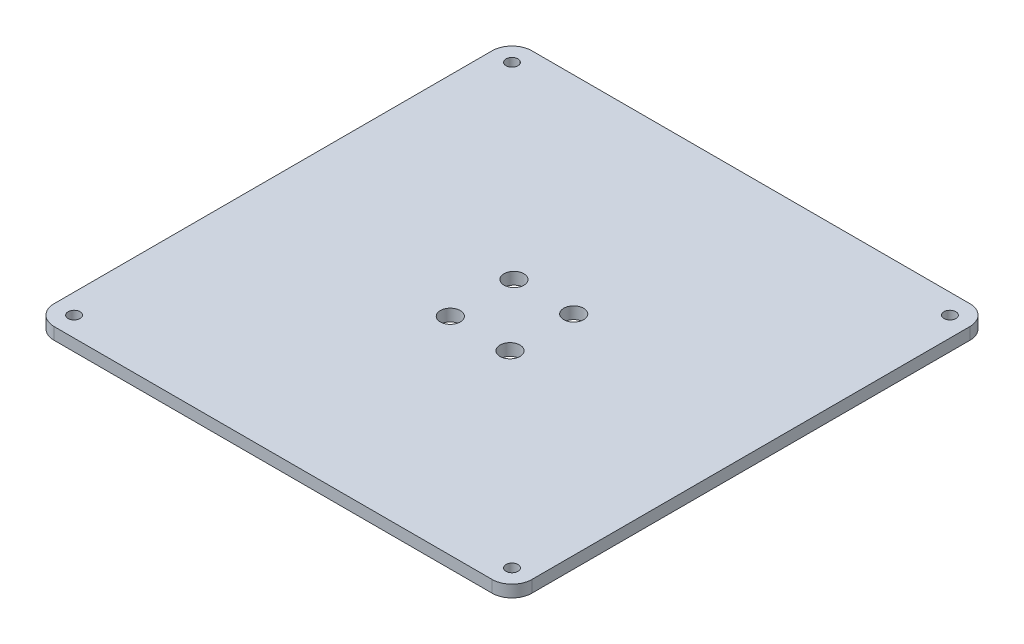
SolidWorks part; units mm, degrees
ref_plane "Alzado" through (0, 0, 0) normal (0, 0, 1) x (1, 0, 0)
ref_plane "Planta" through (0, 0, 0) normal (0, 1, 0) x (1, 0, 0)
ref_plane "Vista lateral" through (0, 0, 0) normal (1, 0, 0) x (0, 0, -1)
sketch "Sketch1" plane through (0, 0, 0) normal (0, 1, 0) x (1, 0, 0)
  line L1 (-7.5, -8) -> (7.5, -8) construction
  line L2 (-7.5, -8) -> (-7.5, 8) construction
  line L3 (-7.5, 8) -> (7.5, 8) construction
  line L4 (7.5, -8) -> (7.5, 8) construction
  line L5 (-7.5, -8) -> (7.5, 8) construction
  line L6 (-7.5, 8) -> (7.5, -8) construction
  line L7 (-60, -60) -> (60, -60)
  line L8 (-60, -60) -> (-60, 60)
  line L9 (-60, 60) -> (60, 60)
  line L10 (60, -60) -> (60, 60)
  circle A0 centre (-7.5, -8) radius 2.5
  circle A1 centre (7.5, 8) radius 2.5
  circle A2 centre (7.5, -8) radius 2.5
  circle A3 centre (-7.5, 8) radius 2.5
  point P0 (0, 0)
  point P10 (0, 0)
  point P16 (-60, 0)
  point P17 (0, -60)
  dimension "D3" = 5
  dimension "D1" = 16
  dimension "D2" = 15
  dimension "D4" = 120
  dimension "D5" = 120
extrude "Boss-Extrude1" add sketch "Sketch1" along normal blind 3
fillet "Fillet1" radius 5 4 edges at (-60, 1.5, -60) (60, 1.5, -60) (60, 1.5, 60) (-60, 1.5, 60)
sketch "Sketch2" plane through (0, 3, 0) normal (0, 1, 0) x (1, 0, 0)
  line L0 (-55, 55) -> (-55, 60) construction
  line L1 (-55, 55) -> (-60, 55) construction
  circle A0 centre (-55, 55) radius 1.5
  dimension "D1" = 3
extrude "Cut-Extrude1" cut sketch "Sketch2" against normal through all
mirror "Mirror3" about plane through (0, 0, 0) normal (0, 0, 1) of "Cut-Extrude1" second plane through (0, 0, 0) second plane normal (1, 0, 0)
